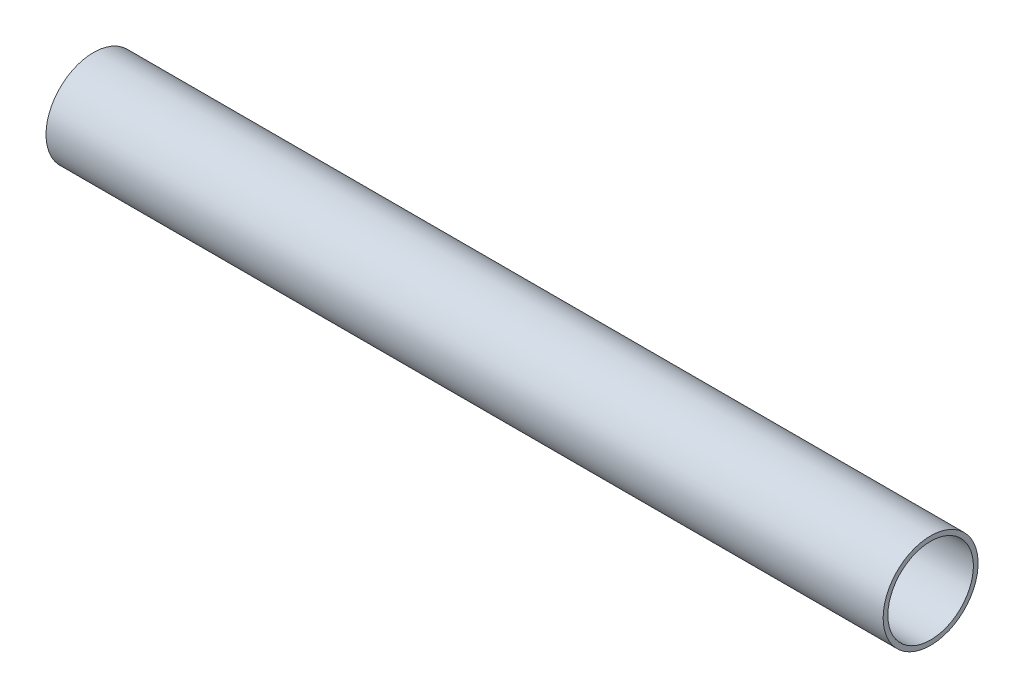
SolidWorks part; units mm, degrees
material "PC High Viscosity"
ref_plane "Front Plane" through (0, 0, 0) normal (0, 0, 1) x (1, 0, 0)
ref_plane "Top Plane" through (0, 0, 0) normal (0, 1, 0) x (1, 0, 0)
ref_plane "Right Plane" through (0, 0, 0) normal (1, 0, 0) x (0, 0, -1)
sketch "Sketch1" plane through (0, 0, 0) normal (1, 0, 0) x (0, 0, -1)
  circle A0 centre (0, 0) radius 15.875
  dimension "D1" = 31.75
extrude "Extrude-Thin1" add sketch "Sketch1" along normal mid plane 279.9115 thin thin type one direction reverse wall 1.5875
